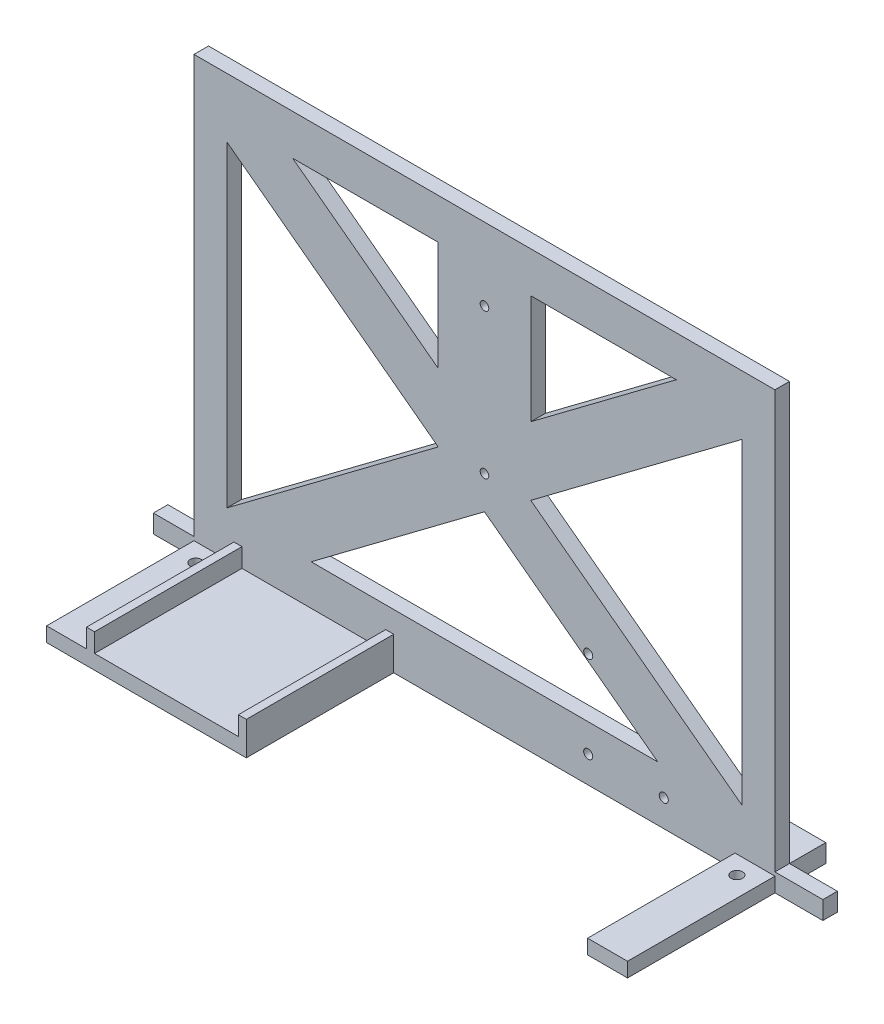
SolidWorks part; units mm, degrees
ref_plane "Front" through (0, 0, 0) normal (0, 0, 1) x (1, 0, 0)
ref_plane "Top" through (0, 0, 0) normal (0, 1, 0) x (1, 0, 0)
ref_plane "Right" through (0, 0, 0) normal (1, 0, 0) x (0, 0, -1)
sketch "Sketch1" plane through (0, 0, 0) normal (0, 0, 1) x (1, 0, 0)
  line L0 (-90.1289, 55.4552) -> (-90.1289, -55.4552)
  line L1 (-101.6, 76.2) -> (101.6, 76.2)
  line L2 (-101.6, 76.2) -> (-101.6, -76.2)
  line L3 (-101.6, -76.2) -> (101.6, -76.2)
  line L4 (101.6, 76.2) -> (101.6, -76.2)
  line L5 (-101.6, 76.2) -> (101.6, -76.2) construction
  line L6 (-101.6, -76.2) -> (101.6, 76.2) construction
  line L7 (0, -55) -> (0, 55) construction
  line L8 (-90.1289, -55.4552) -> (-16.1887, 0)
  line L9 (-16.1887, 0) -> (-90.1289, 55.4552)
  line L10 (55, 0) -> (-55, 0) construction
  line L11 (16.1887, 0) -> (90.1289, 55.4552)
  line L12 (90.1289, -55.4552) -> (16.1887, 0)
  line L13 (90.1289, 55.4552) -> (90.1289, -55.4552)
  line L14 (-16.1887, 61.9912) -> (-16.1887, 23.8125)
  line L15 (-16.1887, 23.8125) -> (-67.0937, 61.9912)
  line L16 (-67.0937, 61.9912) -> (-16.1887, 61.9912)
  line L17 (16.1887, 23.8125) -> (67.0937, 61.9912)
  line L18 (16.1887, 61.9912) -> (16.1887, 23.8125)
  line L19 (67.0937, 61.9912) -> (16.1887, 61.9912)
  line L20 (-60.6282, -57.0175) -> (0, -11.5463)
  line L21 (0, -11.5463) -> (60.6282, -57.0175)
  line L22 (60.6282, -57.0175) -> (-60.6282, -57.0175)
  circle A0 centre (0, 50.8) radius 1.5
  circle A2 centre (0, 0) radius 1.5
  point P0 (0, 0)
  dimension "D3" = 3
  dimension "D4" = 50.8
  dimension "D6" = 19.05
  dimension "D1" = 203.2
  dimension "D2" = 152.4
  dimension "D5" = 25.4
extrude "Boss-Extrude1" add sketch "Sketch1" along normal blind 5.08 contours L4 L1 L2 L3 A2 A0 L19 L17 L18 L9 L8 L0 L11 L13 L12 L15 L16 L14 L21 L22 L20 region at (0, 73.66, 0)
sketch "Sketch2" plane through (0, 0, 5.08) normal (0, 0, 1) x (1, 0, 0)
  line L0 (-101.6, -76.2) -> (101.6, -76.2) construction
  line L1 (-101.6, -76.2) -> (-87.63, -76.2)
  line L2 (-101.6, -76.2) -> (-101.6, -71.12)
  line L3 (-101.6, -71.12) -> (-87.63, -71.12)
  line L4 (-87.63, -76.2) -> (-87.63, -71.12)
  line L5 (0, -55) -> (0, 55) construction
  line L6 (101.6, -71.12) -> (87.63, -71.12)
  line L7 (87.63, -76.2) -> (87.63, -71.12)
  line L8 (101.6, -76.2) -> (87.63, -76.2)
  line L9 (101.6, -76.2) -> (101.6, -71.12)
  line L11 (-87.63, -71.12) -> (-31.75, -71.12)
  line L12 (-87.63, -71.12) -> (-87.63, -76.2)
  line L13 (-87.63, -76.2) -> (-31.75, -76.2)
  line L14 (-31.75, -71.12) -> (-31.75, -76.2)
  line L15 (-87.63, -71.12) -> (-84.836, -71.12)
  line L16 (-87.63, -71.12) -> (-87.63, -64.5258)
  line L17 (-87.63, -64.5258) -> (-84.836, -64.5258)
  line L18 (-84.836, -71.12) -> (-84.836, -64.5258)
  line L19 (-31.75, -71.12) -> (-34.544, -71.12)
  line L20 (-31.75, -71.12) -> (-31.75, -64.5258)
  line L21 (-31.75, -64.5258) -> (-34.544, -64.5258)
  line L22 (-34.544, -71.12) -> (-34.544, -64.5258)
  line M10 (-101.6, -76.2) -> (101.6, -76.2)
  dimension "D1" = 5.08
  dimension "D2" = 55.88
  dimension "D3" = 50.292
  dimension "D4" = 13.97
  dimension "D5" = 31.75
extrude "Boss-Extrude2" add sketch "Sketch2" along normal blind 51.562 contours L4 L3 L2 M10 | L14 L11 L4 M10 | L9 L6 L7 M10 | L16 L15 L18 L17 | L20 L19 L22 L21 region at (-94.615, -73.66, 5.08) region at (94.615, -73.66, 5.08) region at (-59.69, -73.66, 5.08)
sketch "Sketch3" plane through (0, -71.12, 0) normal (0, 1, 0) x (1, 0, 0)
  line L4 (0, -2.794) -> (0, 2.794) construction
  line L10 (-101.6, -5.08) -> (-87.63, -5.08) construction
  line L11 (-101.6, -56.642) -> (-101.6, -5.08) construction
  circle A0 centre (-94.615, -11.43) radius 2
  circle A1 centre (94.615, -11.43) radius 2
  dimension "D1" = 4
  dimension "D2" = 6.35
  dimension "D3" = 6.985
extrude "Cut-Extrude1" cut sketch "Sketch3" against normal up to vertex (5.08 mm away) contours A0 | A1 region at (-94.615, -71.12, 11.43) region at (94.615, -71.12, 11.43) up to point (-101.6, -76.2, 56.642)
sketch "Sketch4" plane through (0, 0, 0) normal (0, 0, -1) x (-1, 0, 0)
  line L0 (0, 2.794) -> (0, -2.794) construction
  line L1 (-101.6, -76.2) -> (-88.9, -76.2)
  line L2 (-101.6, -76.2) -> (-101.6, -69.85)
  line L3 (-101.6, -69.85) -> (-88.9, -69.85)
  line L4 (-101.6, 76.2) -> (-101.6, -76.2)
  line L5 (-101.6, -76.2) -> (101.6, -76.2)
  line L6 (101.6, -76.2) -> (101.6, 76.2)
  line L7 (101.6, 76.2) -> (-101.6, 76.2)
  line L8 (-101.6, 76.2) -> (-101.6, -76.2)
  line L9 (-101.6, -76.2) -> (101.6, -76.2)
  line L10 (101.6, -76.2) -> (101.6, 76.2)
  line L11 (101.6, 76.2) -> (-101.6, 76.2)
  line L12 (-88.9, -76.2) -> (-88.9, -69.85)
  line L13 (101.6, -69.85) -> (88.9, -69.85)
  line L14 (88.9, -76.2) -> (88.9, -69.85)
  line L15 (101.6, -76.2) -> (88.9, -76.2)
  line L16 (101.6, -76.2) -> (101.6, -69.85)
  dimension "D2" = 12.7
  dimension "D3" = 6.35
  dimension "D1" = 0
extrude "Boss-Extrude3" add sketch "Sketch4" along normal blind 12.7 contours L2 L1 L12 L3 | L16 L13 L14 L15
sketch "Sketch5" plane through (101.6, 0, 0) normal (1, 0, 0) x (0, 0, -1)
  line L1 (0, -69.85) -> (-5.08, -69.85)
  line L2 (0, -69.85) -> (0, -76.2)
  line L3 (0, -76.2) -> (-5.08, -76.2)
  line L4 (-5.08, -69.85) -> (-5.08, -76.2)
extrude "Boss-Extrude4" add sketch "Sketch5" along normal blind 16.764
sketch "Sketch6" plane through (-101.6, 0, 0) normal (-1, 0, 0) x (0, 0, 1)
  line L1 (0, -69.85) -> (5.08, -69.85)
  line L2 (0, -69.85) -> (0, -76.2)
  line L3 (0, -76.2) -> (5.08, -76.2)
  line L4 (5.08, -69.85) -> (5.08, -76.2)
extrude "Boss-Extrude5" add sketch "Sketch6" along normal blind 14.224
sketch "Sketch7" plane through (0, 0, 5.08) normal (0, 0, 1) x (1, 0, 0)
  circle A0 centre (36.2876, -66.7853) radius 1.5875
  circle A1 centre (36.2876, -36.4323) radius 1.5875
  circle A3 centre (62.7036, -66.7853) radius 1.5875
  point P8 (0, 0)
  dimension "D1" = 3.175
  dimension "D2" = 30.353
  dimension "D3" = 26.416
extrude "Cut-Extrude2" cut sketch "Sketch7" against normal up to next
